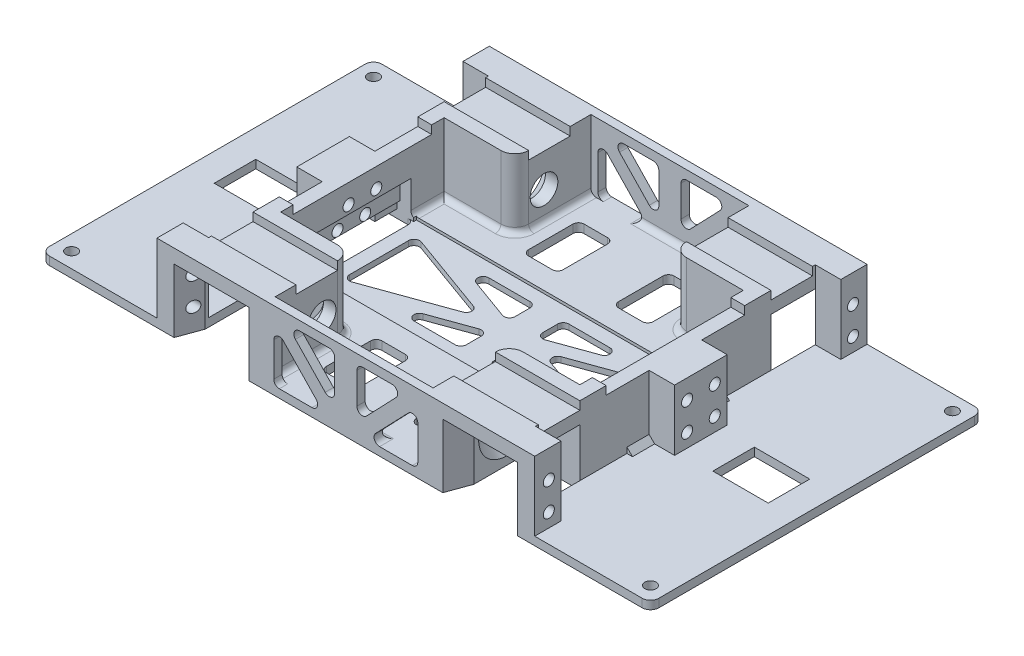
SolidWorks part; units mm, degrees
material "ABS"
ref_plane "前基準面" through (0, 0, 0) normal (0, 0, 1) x (1, 0, 0)
ref_plane "上基準面" through (0, 0, 0) normal (0, 1, 0) x (1, 0, 0)
ref_plane "右基準面" through (0, 0, 0) normal (1, 0, 0) x (0, 0, -1)
sketch "草圖1" plane through (0, 0, 0) normal (0, 1, 0) x (1, 0, 0)
  line L0 (0, 0) -> (0, 78.9859) construction
  line L1 (-110, -60) -> (-59, -60)
  line L2 (-110, -60) -> (-110, 60)
  line L3 (-110, 60) -> (-59, 60)
  line L4 (110, -60) -> (110, 60)
  line L5 (-110, -60) -> (110, 60) construction
  line L6 (-110, 60) -> (110, -60) construction
  line L7 (-38, 60) -> (38, 60)
  line L9 (-59, 60) -> (-59, 34.5)
  line L10 (-59, 34.5) -> (-38, 34.5)
  line L11 (-38, 60) -> (-38, 34.5)
  line L12 (38, 60) -> (38, 34.5)
  line L13 (59, 34.5) -> (38, 34.5)
  line L14 (59, 60) -> (59, 34.5)
  line L15 (0, 0) -> (138.7363, 0) construction
  line L16 (59, -34.5) -> (38, -34.5)
  line L17 (59, -60) -> (59, -34.5)
  line L18 (38, -60) -> (38, -34.5)
  line L19 (-38, -60) -> (-38, -34.5)
  line L20 (-59, -34.5) -> (-38, -34.5)
  line L21 (-59, -60) -> (-59, -34.5)
  line L22 (59, 60) -> (110, 60)
  line L23 (59, -60) -> (110, -60)
  line L24 (-38, -60) -> (38, -60)
  point P0 (0, 0)
  dimension "D1" = 220
  dimension "D2" = 120
  dimension "D3" = 51
  dimension "D4" = 21
  dimension "D5" = 25.5
extrude "填料-伸長1" add sketch "草圖1" along normal blind 3
sketch "草圖9" plane through (0, 3, 0) normal (0, 1, 0) x (1, 0, 0)
  line L1 (-53, -18.5) -> (53, -18.5)
  line L2 (-53, -18.5) -> (-53, 18.5)
  line L3 (-53, 18.5) -> (53, 18.5)
  line L4 (53, -18.5) -> (53, 18.5)
  line L5 (-53, -18.5) -> (53, 18.5) construction
  line L6 (-53, 18.5) -> (53, -18.5) construction
  dimension "D1" = 106
  dimension "D2" = 37
extrude "除料-伸長5" cut sketch "草圖9" against normal blind 1
sketch "草圖2" plane through (0, 3, 0) normal (0, 1, 0) x (1, 0, 0)
  line L0 (0, 0) -> (213.5831, 0) construction
  line L28 (0, 0) -> (0, 101.5292) construction
  line L42 (-59, 34.5) -> (-59, 9.5)
  line L46 (59, 34.5) -> (59, 9.5)
  line L56 (-28.5, 57) -> (28.5, 57)
  line L59 (-28.5, 57) -> (-28.5, 29.5)
  line L92 (28.5, 57) -> (28.5, 29.5)
  line L99 (28.5, -57) -> (28.5, -29.5)
  line L141 (-28.5, -57) -> (28.5, -57)
  line L142 (-28.5, -57) -> (-28.5, -29.5)
  line L143 (-59, 34.5) -> (-59, 60) construction
  line L144 (-59, -34.5) -> (-38, -34.5) construction
  line L145 (28.5, -29.5) -> (54, -29.5)
  line L146 (-28.5, 29.5) -> (-54, 29.5)
  line L148 (-28.5, -29.5) -> (-54, -29.5)
  line L149 (-54, 29.5) -> (-54, -29.5)
  line L150 (28.5, 29.5) -> (54, 29.5)
  line L151 (54, 29.5) -> (54, -29.5)
  line L152 (68.2, 9.5) -> (59, 9.5)
  line L153 (110, 60) -> (59, 60)
  line L154 (59, 60) -> (59, 34.5)
  line L155 (59, 34.5) -> (38, 34.5)
  line L156 (38, 34.5) -> (38, 60)
  line L157 (38, 60) -> (-38, 60)
  line L158 (-38, 60) -> (-38, 34.5)
  line L159 (-38, 34.5) -> (-59, 34.5)
  line L160 (-59, 34.5) -> (-59, 60)
  line L161 (-59, 60) -> (-110, 60)
  line L162 (-110, 60) -> (-110, -60)
  line L163 (-110, -60) -> (-59, -60)
  line L164 (-59, -60) -> (-59, -34.5)
  line L165 (-59, -34.5) -> (-38, -34.5)
  line L166 (-38, -34.5) -> (-38, -60)
  line L167 (-38, -60) -> (38, -60)
  line L168 (38, -60) -> (38, -34.5)
  line L169 (38, -34.5) -> (59, -34.5)
  line L170 (59, -34.5) -> (59, -60)
  line L171 (59, -60) -> (110, -60)
  line L172 (110, -60) -> (110, 60)
  line L175 (59, 34.5) -> (38, 34.5)
  line L176 (38, 34.5) -> (38, 60)
  line L177 (38, 60) -> (-38, 60)
  line L178 (-38, 60) -> (-38, 34.5)
  line L179 (-38, 34.5) -> (-59, 34.5)
  line L185 (-59, -34.5) -> (-38, -34.5)
  line L186 (-38, -34.5) -> (-38, -60)
  line L187 (-38, -60) -> (38, -60)
  line L188 (38, -60) -> (38, -34.5)
  line L189 (38, -34.5) -> (59, -34.5)
  line L193 (-68.2, -9.5) -> (-59, -9.5)
  line L194 (-68.2, -9.5) -> (-68.2, 9.5)
  line L195 (-68.2, 9.5) -> (-59, 9.5)
  line L198 (68.2, -9.5) -> (59, -9.5)
  line L199 (68.2, -9.5) -> (68.2, 9.5)
  line L200 (-59, -9.5) -> (-59, -34.5)
  line L201 (59, -9.5) -> (59, -34.5)
  line L202 (-59, 60) -> (-110, 60) construction
  line L203 (-59, 60) -> (-68.2, 60)
  line L204 (-59, 60) -> (-59, 50.5)
  line L205 (-59, 50.5) -> (-68.2, 50.5)
  line L206 (-68.2, 60) -> (-68.2, 50.5)
  line L207 (59, 50.5) -> (68.2, 50.5)
  line L208 (68.2, 60) -> (68.2, 50.5)
  line L209 (59, 60) -> (68.2, 60)
  line L210 (59, 60) -> (59, 50.5)
  line L211 (59, -60) -> (59, -50.5)
  line L212 (59, -60) -> (68.2, -60)
  line L213 (68.2, -60) -> (68.2, -50.5)
  line L214 (59, -50.5) -> (68.2, -50.5)
  line L215 (-59, -50.5) -> (-68.2, -50.5)
  line L216 (-68.2, -60) -> (-68.2, -50.5)
  line L217 (-59, -60) -> (-68.2, -60)
  line L218 (-59, -60) -> (-59, -50.5)
  dimension "D3" = 9.5
  dimension "D4" = 5
  dimension "D5" = 59
  dimension "D2" = 3
  dimension "D6" = 9.2
  dimension "D7" = 19
  dimension "D8" = 9.5
  dimension "D1" = 0
extrude "填料-伸長2" add sketch "草圖2" along normal blind 25
sketch "草圖4" plane through (0, 0, 0) normal (1, 0, 0) x (0, 0, -1)
  line L0 (0, 0) -> (0, 52.9301) construction
  circle A0 centre (-5, 18) radius 2
  circle A1 centre (-5, 8) radius 2
  circle A2 centre (5, 8) radius 2
  circle A3 centre (5, 18) radius 2
  dimension "D1" = 4
  dimension "D2" = 10
  dimension "D3" = 10
  dimension "D4" = 8
extrude "除料-伸長1" cut sketch "草圖4" against normal through all both and the other way through all
sketch "草圖6" plane through (0, 0, 0) normal (1, 0, 0) x (0, 0, -1)
  line L0 (0, 0) -> (0, 66.2046) construction
  line L1 (60, 0) -> (-60, 0) construction
  circle A0 centre (-40.05, 13) radius 5
  circle A1 centre (40.05, 13) radius 5
  point P8 (-41.4504, 11.6583)
  point P9 (40.05, 13)
  dimension "D1" = 10
  dimension "D2" = 40.05
  dimension "D3" = 13
extrude "除料-伸長2" cut sketch "草圖6" against normal mid plane 90
sketch "草圖7" plane through (-68.2, 0, 0) normal (-1, 0, 0) x (0, 0, 1)
  line L0 (0, 0) -> (0, 45.7304) construction
  line L1 (-60, 0) -> (60, 0) construction
  circle A0 centre (-54.9, 18) radius 2
  circle A1 centre (-54.9, 8) radius 2
  circle A2 centre (54.9, 8) radius 2
  circle A3 centre (54.9, 18) radius 2
  dimension "D2" = 4
  dimension "D3" = 8
  dimension "D1" = 54.9
  dimension "D4" = 10
extrude "除料-伸長3" cut sketch "草圖7" against normal up to next
sketch "草圖8" plane through (68.2, 0, 0) normal (1, 0, 0) x (0, 0, -1)
  line L0 (-60, 0) -> (60, 0) construction
  line L1 (0, 0) -> (0, 48.8676) construction
  circle A0 centre (54.9, 18) radius 2
  circle A1 centre (54.9, 8) radius 2
  circle A4 centre (-54.9, 8) radius 2
  circle A5 centre (-54.9, 18) radius 2
  dimension "D2" = 4
  dimension "D1" = 54.9
  dimension "D3" = 8
  dimension "D4" = 10
extrude "除料-伸長4" cut sketch "草圖8" against normal up to next
sketch "草圖10" plane through (0, 3, 0) normal (0, 1, 0) x (1, 0, 0)
  line L0 (0, 0) -> (0, 80.1377) construction
  line L2 (-58, 17.5) -> (-53, 17.5)
  line L3 (-58, 17.5) -> (-58, -17.5)
  line L4 (-58, -17.5) -> (-53, -17.5)
  line L5 (-53, 17.5) -> (-53, -17.5)
  line L6 (0, 0) -> (26.0198, 0) construction
  line L7 (58, -17.5) -> (53, -17.5)
  line L8 (53, 17.5) -> (53, -17.5)
  line L9 (58, 17.5) -> (58, -17.5)
  line L10 (58, 17.5) -> (53, 17.5)
  dimension "D1" = 5
  dimension "D2" = 35
  dimension "D3" = 53
extrude "除料-伸長6" cut sketch "草圖10" against normal through all and the other way blind 12
sketch "草圖11" plane through (0, 3, 0) normal (0, 1, 0) x (1, 0, 0)
  line L0 (0, 0) -> (0, 44.5869) construction
  line L1 (0, 0) -> (22.9255, 0) construction
  line L2 (-48, 13.5) -> (-48, -13.5)
  line L3 (-48, -13.5) -> (-10.6314, 0)
  line L4 (-10.6314, 0) -> (-48, 13.5)
  line L5 (-33.2843, 13.5) -> (-5, 13.5)
  line L6 (-5, 13.5) -> (-5, 3.2818)
  line L7 (-5, 3.2818) -> (-33.2843, 13.5)
  line L8 (48, -13.5) -> (10.6314, 0)
  line L9 (48, 13.5) -> (48, -13.5)
  line L10 (10.6314, 0) -> (48, 13.5)
  line L11 (5, 13.5) -> (5, 3.2818)
  line L12 (33.2843, 13.5) -> (5, 13.5)
  line L13 (5, 3.2818) -> (33.2843, 13.5)
  line L14 (33.2843, -13.5) -> (5, -13.5)
  line L15 (5, -3.2818) -> (33.2843, -13.5)
  line L16 (5, -13.5) -> (5, -3.2818)
  line L17 (-5, -13.5) -> (-5, -3.2818)
  line L18 (-33.2843, -13.5) -> (-5, -13.5)
  line L19 (-5, -3.2818) -> (-33.2843, -13.5)
  line L20 (22.5, 26.5) -> (10, 26.5)
  line L21 (-53, 18.5) -> (-53, 17.5) construction
  line L22 (53, 18.5) -> (-53, 18.5) construction
  line L23 (110, 60) -> (68.2, 60) construction
  line L24 (110, -60) -> (110, 60) construction
  line L25 (-22.5, 46.5) -> (-10, 46.5)
  line L26 (-22.5, 46.5) -> (-22.5, 26.5)
  line L27 (-22.5, 26.5) -> (-10, 26.5)
  line L28 (-10, 46.5) -> (-10, 26.5)
  line L29 (10, 46.5) -> (10, 26.5)
  line L30 (22.5, 46.5) -> (10, 46.5)
  line L31 (22.5, 46.5) -> (22.5, 26.5)
  line L32 (22.5, -46.5) -> (22.5, -26.5)
  line L33 (22.5, -46.5) -> (10, -46.5)
  line L34 (10, -46.5) -> (10, -26.5)
  line L35 (22.5, -26.5) -> (10, -26.5)
  line L36 (-22.5, -26.5) -> (-10, -26.5)
  line L37 (-10, -46.5) -> (-10, -26.5)
  line L38 (-22.5, -46.5) -> (-10, -46.5)
  line L39 (-22.5, -46.5) -> (-22.5, -26.5)
  line L40 (-110, 60) -> (-110, -60) construction
  line L41 (-100, 7.5) -> (-80, 7.5)
  line L42 (-100, 7.5) -> (-100, -7.5)
  line L43 (-100, -7.5) -> (-80, -7.5)
  line L44 (-80, 7.5) -> (-80, -7.5)
  line L45 (100, -7.5) -> (80, -7.5)
  line L46 (80, 7.5) -> (80, -7.5)
  line L47 (100, 7.5) -> (80, 7.5)
  line L48 (100, 7.5) -> (100, -7.5)
  circle A0 centre (104.5, 54.5) radius 2.05
  circle A1 centre (-104.5, 54.5) radius 2.05
  circle A2 centre (-104.5, -54.5) radius 2.05
  circle A3 centre (104.5, -54.5) radius 2.05
  dimension "D3" = 4.1
  dimension "D10" = 10
  dimension "D2" = 5.5
  dimension "D4" = 5
  dimension "D5" = 5
  dimension "D6" = 5
  dimension "D7" = 10
  dimension "D8" = 15
  dimension "D9" = 20
  dimension "D11" = 5.5
  dimension "D12" = 20
  dimension "D13" = 12.5
  dimension "D14" = 20
  dimension "D15" = 8
extrude "除料-伸長7" cut sketch "草圖11" against normal through all
sketch "草圖12" plane through (0, 28, 0) normal (0, 1, 0) x (1, 0, 0)
  line L0 (0, 0) -> (0, 65.905) construction
  line L1 (0, 0) -> (64.3084, 0) construction
  line L2 (-68.2, 60) -> (-110, 60) construction
  line L3 (-59, 60) -> (-28.5, 60)
  line L4 (-59, 60) -> (-59, 29.5)
  line L5 (-59, 29.5) -> (-28.5, 29.5)
  line L6 (-28.5, 60) -> (-28.5, 29.5)
  line L7 (-59, 60) -> (-68.2, 60) construction
  line L8 (-28.5, 57) -> (-28.5, 29.5) construction
  line L9 (59, 29.5) -> (28.5, 29.5)
  line L10 (28.5, 60) -> (28.5, 29.5)
  line L11 (59, 60) -> (28.5, 60)
  line L12 (59, 60) -> (59, 29.5)
  line L13 (59, -60) -> (59, -29.5)
  line L14 (59, -60) -> (28.5, -60)
  line L15 (28.5, -60) -> (28.5, -29.5)
  line L16 (59, -29.5) -> (28.5, -29.5)
  line L17 (-59, -29.5) -> (-28.5, -29.5)
  line L18 (-28.5, -60) -> (-28.5, -29.5)
  line L19 (-59, -60) -> (-28.5, -60)
  line L20 (-59, -60) -> (-59, -29.5)
  line L23 (-59, 50.5) -> (-59, 60) construction
extrude "填料-伸長3" add sketch "草圖12" against normal blind 5
sketch "草圖13" plane through (0, 0, 0) normal (0, 0, 1) x (1, 0, 0)
  line L0 (0, 0) -> (0, 45.7733) construction
  line L1 (-26, 22.2892) -> (-26, 3)
  line L2 (-26, 3) -> (-7.5, 3)
  line L3 (-7.5, 3) -> (-26, 22.2892)
  line L4 (-21.4241, 24.7416) -> (-4, 6.5742)
  line L5 (-4, 6.5742) -> (-4, 24.7416)
  line L6 (-4, 24.7416) -> (-21.4241, 24.7416)
  line L7 (26, 3) -> (7.5, 3)
  line L8 (26, 22.2892) -> (26, 3)
  line L9 (7.5, 3) -> (26, 22.2892)
  line L10 (4, 6.5742) -> (4, 24.7416)
  line L11 (21.4241, 24.7416) -> (4, 6.5742)
  line L12 (4, 24.7416) -> (21.4241, 24.7416)
  line L13 (-38, 23) -> (-38, 0) construction
  line L14 (-38, 0) -> (38, 0) construction
  dimension "D1" = 12
  dimension "D2" = 3
  dimension "D3" = 8
  dimension "D4" = 15
  dimension "D6" = 5
extrude "除料-伸長8" cut sketch "草圖13" against normal through all both and the other way through all
sketch "草圖14" plane through (0, 28, 0) normal (0, 1, 0) x (1, 0, 0)
  line L0 (0, 0) -> (124.6571, 0) construction
  line L1 (0, 0) -> (0, 107.7379) construction
  line L2 (-28.5, 57) -> (-28.5, 29.5) construction
  line L3 (-59, 52.5) -> (-28.5, 52.5)
  line L4 (-59, 52.5) -> (-59, 32.5)
  line L5 (-59, 32.5) -> (-28.5, 32.5)
  line L6 (-28.5, 52.5) -> (-28.5, 32.5)
  line L7 (-68.2, 50.5) -> (-59, 50.5) construction
  line L8 (-59, 50.5) -> (-59, 9.5) construction
  line L9 (59, 32.5) -> (28.5, 32.5)
  line L10 (28.5, 52.5) -> (28.5, 32.5)
  line L11 (59, 52.5) -> (28.5, 52.5)
  line L12 (59, 52.5) -> (59, 32.5)
  line L13 (59, -52.5) -> (59, -32.5)
  line L14 (59, -52.5) -> (28.5, -52.5)
  line L15 (28.5, -52.5) -> (28.5, -32.5)
  line L16 (59, -32.5) -> (28.5, -32.5)
  line L17 (-59, -32.5) -> (-28.5, -32.5)
  line L18 (-28.5, -52.5) -> (-28.5, -32.5)
  line L19 (-59, -52.5) -> (-28.5, -52.5)
  line L20 (-59, -52.5) -> (-59, -32.5)
  dimension "D1" = 20
  dimension "D2" = 2
extrude "填料-伸長8" add sketch "草圖14" against normal blind 7.5
sketch "草圖15" plane through (0, 28, 0) normal (0, 1, 0) x (1, 0, 0)
  line L0 (0, 0) -> (97.5522, 0) construction
  line L1 (0, 0) -> (0, 87.1305) construction
  line L2 (-60, 49.5) -> (60, 49.5)
  line L3 (-60, 49.5) -> (-60, 34.5)
  line L4 (-60, 34.5) -> (60, 34.5)
  line L5 (60, 49.5) -> (60, 34.5)
  line L6 (-60, -34.5) -> (60, -34.5)
  line L7 (60, -49.5) -> (60, -34.5)
  line L8 (-60, -49.5) -> (60, -49.5)
  line L9 (-60, -49.5) -> (-60, -34.5)
  line L11 (28.5, 57) -> (-28.5, 57) construction
  line L12 (-68.2, 25) -> (68.2, 25)
  line L13 (-68.2, 25) -> (-68.2, -25)
  line L14 (-68.2, -25) -> (68.2, -25)
  line L15 (68.2, 25) -> (68.2, -25)
  dimension "D1" = 15
  dimension "D2" = 7.5
  dimension "D3" = 120
extrude "除料-伸長9" cut sketch "草圖15" against normal blind 3
chamfer "導角1" distance 5 angle 45 4 edges at (38, 13, -35.05) (-38, 13, -45.05) (38, 13, 45.05) (-38, 13, 35.05)
fillet "圓角1" radius 3 4 edges at (-110, 1.5, 60) (110, 1.5, 60) (110, 1.5, -60) (-110, 1.5, -60)
chamfer "導角2" distance 6 angle 45 2 edges at (58, 0, 0) (-58, 0, 0)
chamfer "導角3" distance 3 angle 70 8 edges at (-38, 11.5, -60) (-59, 11.5, -60) (38, 11.5, -60) (59, 11.5, -60) (59, 11.5, 60) (38, 11.5, 60) (-38, 11.5, 60) (-59, 11.5, 60)
fillet "圓角2" radius 5 4 edges at (-28.5, 15.5, 29.5) (-28.5, 15.5, -29.5) (28.5, 15.5, 29.5) (28.5, 15.5, -29.5)
fillet "圓角3" radius 2 82 edges at (-28.5, 3, -45.75) (-54, 3, -23.5) (-43.75, 3, 29.5) (28.5, 3, 45.75) (54, 3, 23.5) (43.75, 3, -29.5) (-28.5, 3, 45.75) (-43.75, 3, -29.5) (43.75, 3, 29.5) (28.5, 3, -45.75) (-29.9645, 3, 30.9645) (-29.9645, 3, -30.9645) (29.9645, 3, 30.9645) (29.9645, 3, -30.9645) (-54, 3, 23.5) (54, 3, -23.5) (53, 3, -18) (-53, 3, 18) (53.5, 3, 17.5) (53.5, 3, -17.5) (-53.5, 3, -17.5) (-53.5, 3, 17.5) (48, 1, -13.5) (48, 1, 13.5) (10.6314, 1, 0) (5, 1, -13.5) (33.2843, 1, -13.5) (5, 1, -3.2818) (-5, 1, -3.2818) (-33.2843, 1, -13.5) (-5, 1, -13.5) (-48, 1, -13.5) (-10.6314, 1, 0) (-48, 1, 13.5) (-22.5, 1.5, 46.5) (-22.5, 1.5, 26.5) (-10, 1.5, 26.5) (-10, 1.5, 46.5) (22.5, 1.5, 46.5) (10, 1.5, 46.5) (10, 1.5, 26.5) (22.5, 1.5, 26.5) (22.5, 1.5, -46.5) (22.5, 1.5, -26.5) (10, 1.5, -26.5) (10, 1.5, -46.5) (5, 1, 3.2818) (33.2843, 1, 13.5) (5, 1, 13.5) (-5, 1, 13.5) (-33.2843, 1, 13.5) (-5, 1, 3.2818) (-22.5, 1.5, -26.5) (-22.5, 1.5, -46.5) (-10, 1.5, -46.5) (-10, 1.5, -26.5) (53, 3, 18) (-53, 3, -18) (-21.4241, 24.7416, 58.5) (-4, 24.7416, 58.5) (-4, 6.5742, 58.5) (-21.4241, 24.7416, -58.5) (-4, 24.7416, -58.5) (-4, 6.5742, -58.5) (26, 22.2892, 58.5) (7.5, 3, 58.5) (26, 3, -58.5) (26, 3, 58.5) (26, 22.2892, -58.5) (7.5, 3, -58.5) (21.4241, 24.7416, 58.5) (4, 6.5742, 58.5) (4, 24.7416, 58.5) (21.4241, 24.7416, -58.5) (4, 6.5742, -58.5) (4, 24.7416, -58.5) (-26, 22.2892, 58.5) (-26, 3, 58.5) (-7.5, 3, -58.5) (-7.5, 3, 58.5) (-26, 22.2892, -58.5) (-26, 3, -58.5)
